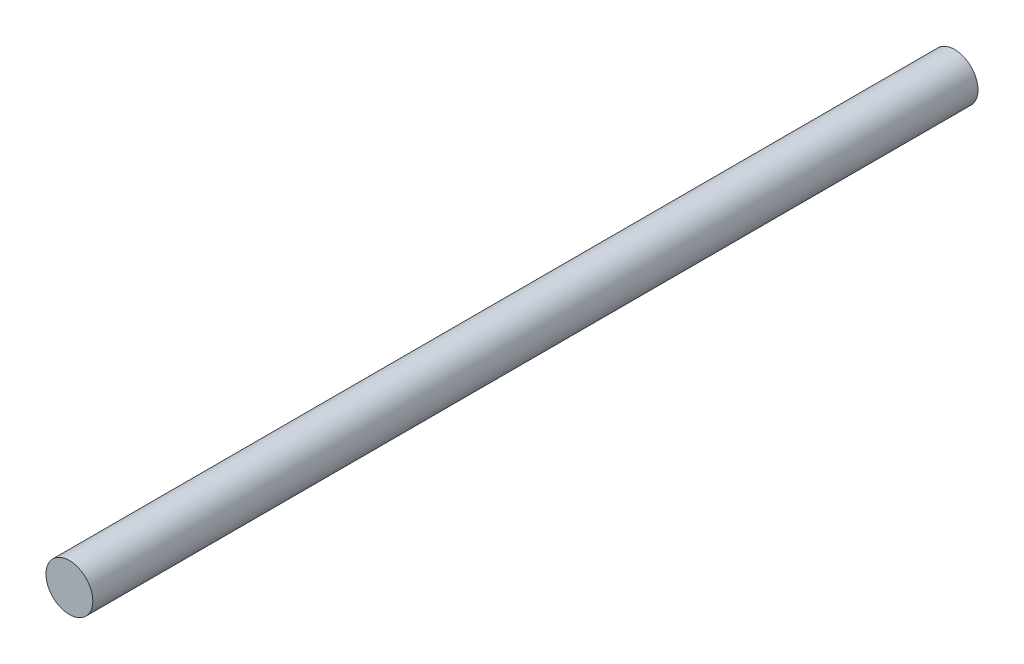
SolidWorks part; units mm, degrees
ref_plane "Front Plane" through (0, 0, 0) normal (0, 0, 1) x (1, 0, 0)
ref_plane "Top Plane" through (0, 0, 0) normal (0, 1, 0) x (1, 0, 0)
ref_plane "Right Plane" through (0, 0, 0) normal (1, 0, 0) x (0, 0, -1)
sketch "Sketch1" plane through (0, 0, 0) normal (0, 0, 1) x (1, 0, 0)
  circle A0 centre (0, 0) radius 1.5875
  dimension "D1" = 3.175
extrude "Boss-Extrude1" add sketch "Sketch1" along normal blind 60
